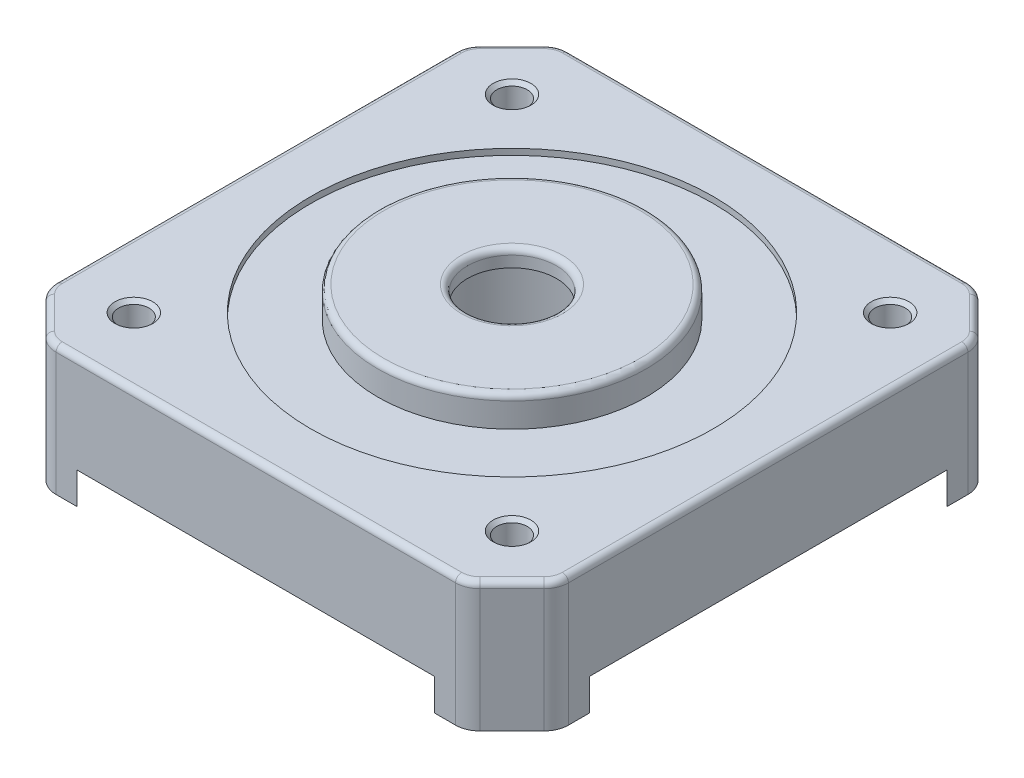
SolidWorks part; units mm, degrees
ref_plane "Спереди" through (0, 0, 0) normal (0, 0, 1) x (1, 0, 0)
ref_plane "Сверху" through (0, 0, 0) normal (0, 1, 0) x (1, 0, 0)
ref_plane "Справа" through (0, 0, 0) normal (1, 0, 0) x (0, 0, -1)
sketch "Эскиз1" plane through (0, 0, 0) normal (0, 1, 0) x (1, 0, 0)
  line L0 (-21, 17.2) -> (-17.2, 21)
  line L1 (-17.2, -21) -> (17.2, -21)
  line L2 (-21, -17.2) -> (-21, 17.2)
  line L3 (-17.2, 21) -> (17.2, 21)
  line L4 (21, -17.2) -> (21, 17.2)
  line L5 (-21, -21) -> (21, 21) construction
  line L6 (-21, 21) -> (21, -21) construction
  line L7 (17.2, 21) -> (21, 17.2)
  line L8 (17.2, -21) -> (21, -17.2)
  line L9 (-21, -17.2) -> (-17.2, -21)
  line L10 (-15.5, -15.5) -> (15.5, -15.5) construction
  line L11 (-15.5, -15.5) -> (-15.5, 15.5) construction
  line L12 (-15.5, 15.5) -> (15.5, 15.5) construction
  line L13 (15.5, -15.5) -> (15.5, 15.5) construction
  line L14 (-15.5, -15.5) -> (15.5, 15.5) construction
  line L15 (-15.5, 15.5) -> (15.5, -15.5) construction
  circle A0 centre (-15.5, 15.5) radius 1.25
  circle A1 centre (15.5, 15.5) radius 1.25
  circle A2 centre (15.5, -15.5) radius 1.25
  circle A3 centre (-15.5, -15.5) radius 1.25
  circle A4 centre (0, 0) radius 3.65
  circle A5 centre (0, 0) radius 16.5
  circle A6 centre (0, 0) radius 11
  arc A7 (-21, -14.641) -> (-14.641, -21) centre (0, 0) ccw
  arc A8 (-14.641, 21) -> (-21, 14.641) centre (0, 0) ccw
  arc A9 (21, 14.641) -> (14.641, 21) centre (0, 0) ccw
  arc A10 (14.641, -21) -> (21, -14.641) centre (0, 0) ccw
  circle A11 centre (-15.5, 15.5) radius 2.65
  circle A12 centre (15.5, 15.5) radius 2.65
  circle A13 centre (15.5, -15.5) radius 2.65
  circle A14 centre (-15.5, -15.5) radius 2.65
  point P0 (0, 0)
  point P13 (0, 0)
  dimension "D9" = 2.5
  dimension "D10" = 5.3
  dimension "D11" = 7.3
  dimension "D12" = 22
  dimension "D13" = 33
  dimension "D14" = 25.6
  dimension "D1" = 3.8
  dimension "D2" = 3.8
  dimension "D3" = 3.8
  dimension "D4" = 3.8
  dimension "D5" = 3.8
  dimension "D6" = 3.8
  dimension "D7" = 3.8
  dimension "D8" = 3.8
  dimension "D15" = 31
  dimension "D16" = 42
extrude "Бобышка-Вытянуть1" add sketch "Эскиз1" along normal blind 8 contours L1 A10 L4 A9 L3 A8 L2 A7 A14 A13 A12 A11 A5 | A13 A2 | A14 A3 | A11 A0 | A12 A1 | A7 L2 L9 L1 | A8 L3 L0 L2 | A9 L4 L7 L3 | A10 L1 L8 L4 region at (-18.5132, 0, -18.5132) region at (-17.6819, 0, -17.6819) region at (-18.5132, 0, 18.5132) region at (18.5132, 0, -18.5132) region at (18.5132, 0, 18.5132) region at (-18.075, 0, -15.5) region at (12.925, 0, -15.5) region at (12.925, 0, 15.5) region at (-18.075, 0, 15.5)
extrude "Бобышка-Вытянуть2" add sketch "Эскиз1<3>" along normal blind 7.5 contours A5 A6 region at (-16.0333, 0, 0)
sketch "Эскиз1<3>" plane through (0, 0, 0) normal (0, 1, 0) x (1, 0, 0) same geometry as "Эскиз1"
extrude "Бобышка-Вытянуть3" add sketch "Эскиз1<4>" along normal blind 10 contours A6 A4 region at (-10.6889, 0, 0)
sketch "Эскиз1<4>" plane through (0, 0, 0) normal (0, 1, 0) x (1, 0, 0) same geometry as "Эскиз1"
extrude "Бобышка-Вытянуть4" add sketch "Эскиз1<5>" against normal blind 2.6 contours A7 L2 L9 L1 | A10 L1 L8 L4 | A8 L3 L0 L2 | A9 L4 L7 L3 region at (-18.5132, 0, -18.5132) region at (-18.5132, 0, 18.5132) region at (18.5132, 0, -18.5132) region at (18.5132, 0, 18.5132)
sketch "Эскиз1<5>" plane through (0, 0, 0) normal (0, 1, 0) x (1, 0, 0) same geometry as "Эскиз1"
sketch "Эскиз2" plane through (0, 0, 0) normal (0, -1, 0) x (1, 0, 0)
  circle A0 centre (0, 0) radius 8
extrude "Вырез-Вытянуть1" cut sketch "Эскиз2" against normal blind 8.6
fillet "Скругление1" radius 2 8 edges at (21, 2.7, 17.2) (17.2, 2.7, 21) (-17.2, 2.7, 21) (-21, 2.7, 17.2) (-21, 2.7, -17.2) (-17.2, 2.7, -21) (17.2, 2.7, -21) (21, 2.7, -17.2)
fillet "Скругление2" radius 0.5 18 edges at (-17.1369, 8, 20.8478) (-19.1, 8, 19.1) (-20.8478, 8, 17.1369) (-21, 8, 0) (-20.8478, 8, -17.1369) (-19.1, 8, -19.1) (-17.1369, 8, -20.8478) (0, 8, -21) (17.1369, 8, -20.8478) (19.1, 8, -19.1) (20.8478, 8, -17.1369) (21, 8, 0) (20.8478, 8, 17.1369) (19.1, 8, 19.1) (17.1369, 8, 20.8478) (0, 8, 21) (0, 10, 3.65) (0, 10, 11)
chamfer "Фаска1" distance 0.3 angle 45 4 edges at (-15.5, 8, 16.75) (-15.5, 8, -14.25) (15.5, 8, -14.25) (15.5, 8, 16.75)
